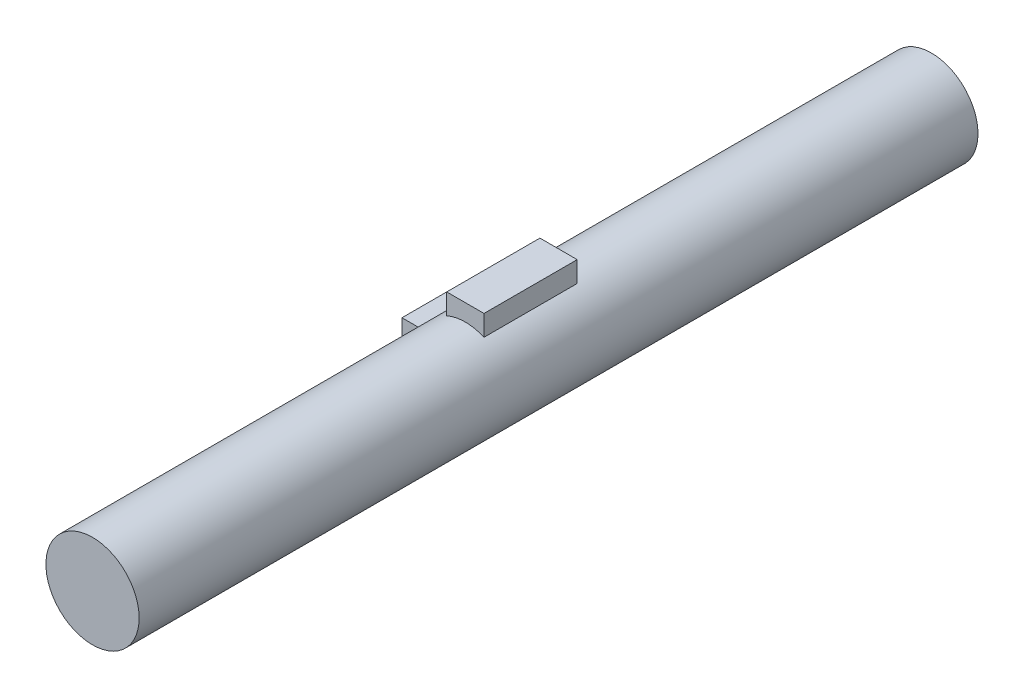
SolidWorks part; units mm, degrees
ref_plane "Front Plane" through (0, 0, 0) normal (0, 0, 1) x (1, 0, 0)
ref_plane "Top Plane" through (0, 0, 0) normal (0, 1, 0) x (1, 0, 0)
ref_plane "Right Plane" through (0, 0, 0) normal (1, 0, 0) x (0, 0, -1)
sketch "Sketch2" plane through (0, 0, 0) normal (0, 0, 1) x (1, 0, 0)
  line L1 (-6.8, 2) -> (0, 2)
  line L2 (-6.8, 2) -> (-6.8, -2)
  line L3 (-6.8, -2) -> (0, -2)
  line L4 (0, 2) -> (0, -2)
  line L5 (-6.8, 2) -> (0, -2) construction
  line L6 (-6.8, -2) -> (0, 2) construction
  line L7 (-2, 6.8) -> (2, 6.8)
  line L8 (-2, 6.8) -> (-2, 0)
  line L9 (-2, 0) -> (2, 0)
  line L10 (2, 6.8) -> (2, 0)
  line L11 (-2, 6.8) -> (2, 0) construction
  line L12 (-2, 0) -> (2, 6.8) construction
  circle A0 centre (0, 0) radius 5
  point P3 (-3.4, 0)
  point P10 (0, 3.4)
  dimension "D1" = 10
  dimension "D2" = 4
  dimension "D4" = 0
  dimension "D3" = 6.8
  dimension "D5" = 4
  dimension "D6" = 6.8
  dimension "D7" = 0
  dimension "D8" = 0
extrude "Boss-Extrude1" add sketch "Sketch2" along normal blind 10 contours L7 L10 L9 L8 | L2 L3 L4 L1 | A0
extrude "Boss-Extrude3" add sketch "Sketch2<4>" along normal blind 50 contours A0
sketch "Sketch2<4>" plane through (0, 0, 0) normal (0, 0, 1) x (1, 0, 0) same geometry as "Sketch2"
extrude "Boss-Extrude4" add sketch "Sketch2<5>" against normal blind 40 contours A0
sketch "Sketch2<5>" plane through (0, 0, 0) normal (0, 0, 1) x (1, 0, 0) same geometry as "Sketch2"
